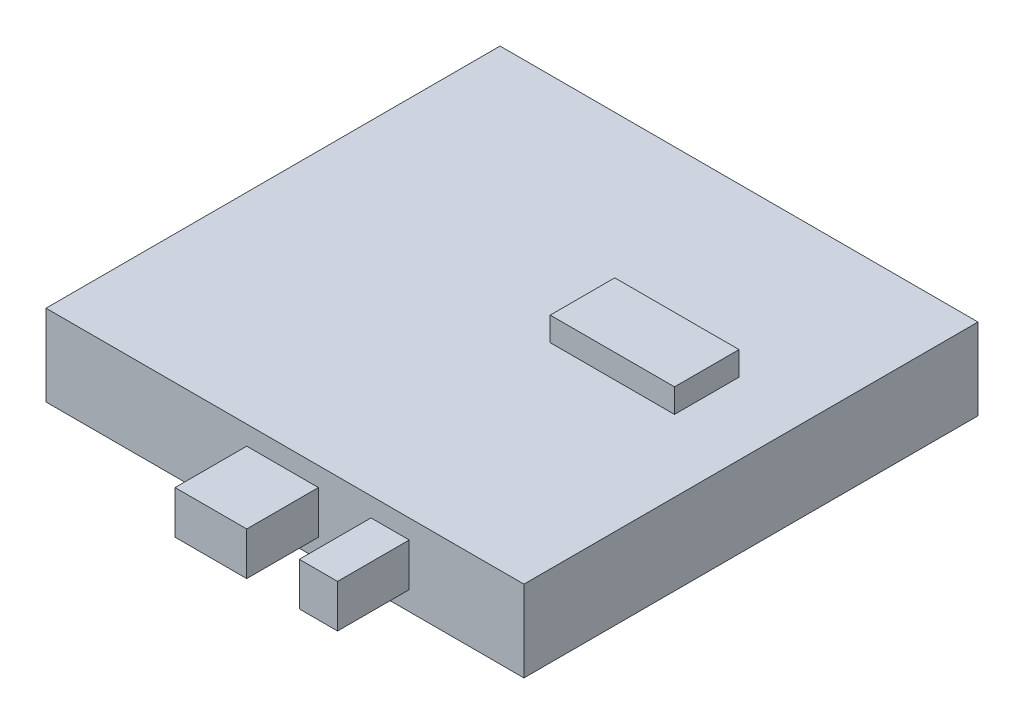
SolidWorks part; units mm, degrees
ref_plane "Front Plane" through (0, 0, 0) normal (0, 0, 1) x (1, 0, 0)
ref_plane "Top Plane" through (0, 0, 0) normal (0, 1, 0) x (1, 0, 0)
ref_plane "Right Plane" through (0, 0, 0) normal (1, 0, 0) x (0, 0, -1)
sketch "Sketch1" plane through (0, 0, 0) normal (0, 1, 0) x (1, 0, 0)
  line L0 (24.9315, -43.415) -> (35.9315, -43.415)
  line L1 (-32.0685, 51.585) -> (67.9315, 51.585)
  line L2 (-32.0685, 51.585) -> (-32.0685, -43.415)
  line L3 (-32.0685, -43.415) -> (9.9315, -43.415)
  line L4 (67.9315, 51.585) -> (67.9315, -43.415)
  line L5 (26.9315, 16.585) -> (52.9315, 16.585)
  line L6 (26.9315, 16.585) -> (26.9315, 3.085)
  line L7 (26.9315, 3.085) -> (52.9315, 3.085)
  line L8 (52.9315, 16.585) -> (52.9315, 3.085)
  line L10 (9.9315, -43.415) -> (9.9315, -58.415)
  line L11 (9.9315, -58.415) -> (24.9315, -58.415)
  line L12 (24.9315, -43.415) -> (24.9315, -58.415)
  line L14 (43.9315, -43.415) -> (43.9315, -58.415)
  line L15 (43.9315, -58.415) -> (35.9315, -58.415)
  line L16 (35.9315, -43.415) -> (35.9315, -58.415)
  line L17 (43.9315, -43.415) -> (67.9315, -43.415)
  dimension "D1" = 100
  dimension "D2" = 95
  dimension "D3" = 26
  dimension "D4" = 13.5
  dimension "D5" = 15
  dimension "D6" = 35
  dimension "D7" = 42
  dimension "D8" = 24
  dimension "D9" = 15
  dimension "D10" = 8
  dimension "D11" = 15
extrude "Boss-Extrude9" add sketch "Sketch1" along normal blind 17 contours L14 L17 L4 L1 L2 L3 L10 L11 L12 L0 L16 L15 L5 L8 L7 L6 | L6 L5 L8 L7 region at (17.3843, 0, -1.8738)
sketch "Sketch5" plane through (0, 17, 0) normal (0, 1, 0) x (1, 0, 0)
  line L0 (67.9315, 51.585) -> (67.9315, -43.415) construction
  line L1 (26.9315, 16.585) -> (52.9315, 16.585)
  line L2 (26.9315, 16.585) -> (26.9315, 3.085)
  line L3 (26.9315, 3.085) -> (52.9315, 3.085)
  line L4 (52.9315, 16.585) -> (52.9315, 3.085)
  line L5 (-32.0685, 51.585) -> (67.9315, 51.585) construction
  dimension "D1" = 26
  dimension "D2" = 13.5
  dimension "D3" = 15
  dimension "D4" = 35
extrude "Boss-Extrude10" add sketch "Sketch5" along normal blind 5
sketch "Sketch6" plane through (0, 17, 0) normal (0, 1, 0) x (1, 0, 0)
  line L1 (24.9315, -58.415) -> (9.9315, -58.415)
  line L2 (24.9315, -58.415) -> (24.9315, -43.415)
  line L3 (24.9315, -43.415) -> (9.9315, -43.415)
  line L4 (9.9315, -58.415) -> (9.9315, -43.415)
  line L5 (43.9315, -58.415) -> (35.9315, -58.415)
  line L6 (43.9315, -58.415) -> (43.9315, -43.415)
  line L7 (43.9315, -43.415) -> (35.9315, -43.415)
  line L8 (35.9315, -58.415) -> (35.9315, -43.415)
extrude "Cut-Extrude1" cut sketch "Sketch6" against normal blind 4
sketch "Sketch7" plane through (0, 0, 0) normal (0, -1, 0) x (1, 0, 0)
  line L0 (9.9315, 58.415) -> (24.9315, 58.415) construction
  line L1 (24.9315, 58.415) -> (9.9315, 58.415)
  line L2 (24.9315, 58.415) -> (24.9315, 43.415)
  line L3 (24.9315, 43.415) -> (9.9315, 43.415)
  line L4 (9.9315, 58.415) -> (9.9315, 43.415)
  line L5 (43.9315, 58.415) -> (35.9315, 58.415) construction
  line L6 (35.9315, 58.415) -> (43.9315, 58.415)
  line L7 (35.9315, 58.415) -> (35.9315, 43.415)
  line L8 (35.9315, 43.415) -> (43.9315, 43.415)
  line L9 (43.9315, 58.415) -> (43.9315, 43.415)
  line L10 (35.9315, 43.415) -> (35.9315, 58.415) construction
  line L11 (43.9315, 43.415) -> (43.9315, 58.415) construction
extrude "Cut-Extrude2" cut sketch "Sketch7" against normal blind 4
